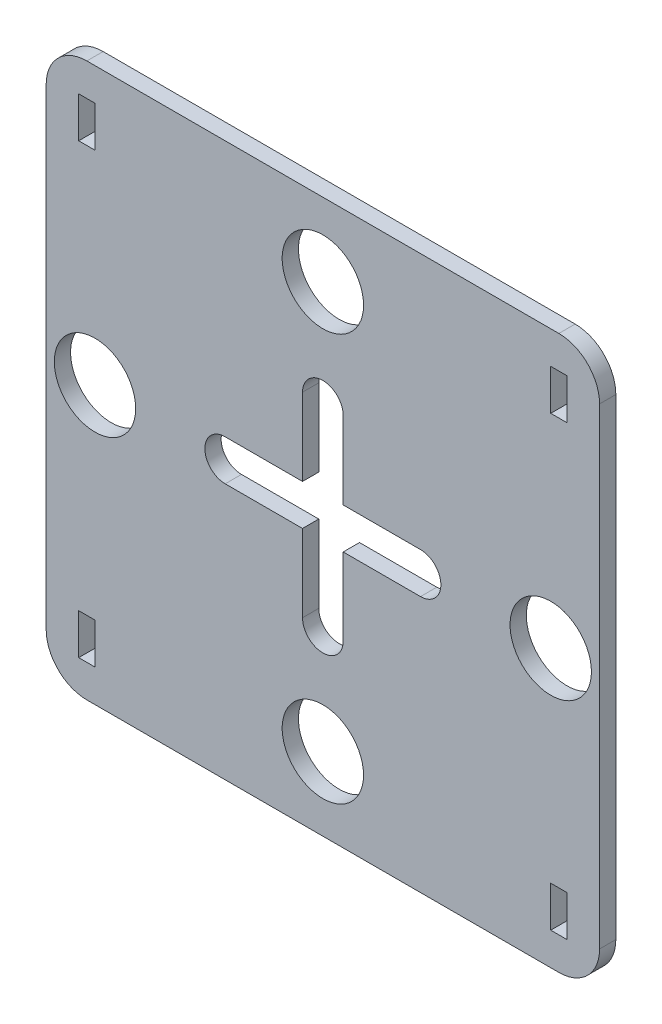
SolidWorks part; units mm, degrees
material "Thornel Mat VMA"
ref_plane "Ön Düzlem" through (0, 0, 0) normal (0, 0, 1) x (1, 0, 0)
ref_plane "Üst Düzlem" through (0, 0, 0) normal (0, 1, 0) x (1, 0, 0)
ref_plane "Sağ Düzlem" through (0, 0, 0) normal (1, 0, 0) x (0, 0, -1)
sketch "Sketch1" plane through (0, 0, 0) normal (0, 0, 1) x (1, 0, 0)
  line L0 (-28, 25) -> (28, 25) construction
  line L1 (30, 30) -> (28, 30)
  line L2 (30, 30) -> (30, 25)
  line L3 (-30, -30) -> (30, -30) construction
  line L4 (-30, -30) -> (-30, 30) construction
  line L5 (-30, 30) -> (30, 30) construction
  line L6 (30, -30) -> (30, 30) construction
  line L7 (-34, 34) -> (34, 34)
  line L8 (-34, 34) -> (-34, -34)
  line L9 (-34, -34) -> (34, -34)
  line L10 (34, 34) -> (34, -34)
  line L11 (30, 25) -> (28, 25)
  line L12 (28, 30) -> (28, 25)
  line L13 (30, -30) -> (28, -30)
  line L14 (30, -30) -> (30, -25)
  line L15 (30, -25) -> (28, -25)
  line L16 (28, -30) -> (28, -25)
  line L17 (-30, -30) -> (-28, -30)
  line L18 (-30, -30) -> (-30, -25)
  line L19 (-30, -25) -> (-28, -25)
  line L20 (-28, -30) -> (-28, -25)
  line L21 (-30, 30) -> (-28, 30)
  line L22 (-30, 30) -> (-30, 25)
  line L23 (-30, 25) -> (-28, 25)
  line L24 (-28, 30) -> (-28, 25)
  line L25 (28, 25) -> (28, -25) construction
  line L26 (-28, -25) -> (-28, 25) construction
  line L27 (-28, -25) -> (28, -25) construction
  line L28 (-12, 0) -> (12, 0) construction
  line L29 (-12, 2.5) -> (12, 2.5)
  line L30 (-12, -2.5) -> (12, -2.5)
  line L31 (0, 12) -> (0, -12) construction
  line L32 (2.5, 12) -> (2.5, -12)
  line L33 (-2.5, 12) -> (-2.5, -12)
  circle A0 centre (0, 25) radius 5
  circle A1 centre (28, 0) radius 5
  circle A2 centre (0, -25) radius 5
  circle A3 centre (-28, 0) radius 5
  arc A4 (-12, 2.5) -> (-12, -2.5) centre (-12, 0) ccw
  arc A5 (12, -2.5) -> (12, 2.5) centre (12, 0) ccw
  arc A6 (2.5, 12) -> (-2.5, 12) centre (0, 12) ccw
  arc A7 (-2.5, -12) -> (2.5, -12) centre (0, -12) ccw
  point P30 (0, 0)
  point P38 (0, 0)
  dimension "D13" = 16
  dimension "D1" = 2
  dimension "D2" = 4
  dimension "D3" = 4
  dimension "D4" = 4
  dimension "D5" = 4
  dimension "D6" = 5
  dimension "D7" = 2
  dimension "D8" = 5
  dimension "D9" = 2
  dimension "D10" = 5
  dimension "D11" = 2
  dimension "D12" = 5
  dimension "D14" = 16
  dimension "D15" = 5
  dimension "D16" = 24
  dimension "D17" = 5
extrude "Boss-Extrude1" add sketch "Sketch1" along normal blind 2 contours L10 L7 L8 L9 A7 L33 L30 A4 L29 A6 L32 A5 A3 A2 A1 A0 L13 L16 L15 L14 L12 L1 L2 L11 L20 L17 L18 L19 L21 L24 L23 L22 region at (0, 33.0383, 0)
fillet "Fillet2" radius 5 1 edges at (34, 34, 1)
fillet "Fillet3" radius 5 1 edges at (-34, 34, 1)
fillet "Fillet4" radius 5 1 edges at (-34, -34, 1)
fillet "Fillet5" radius 5 1 edges at (34, -34, 1)
